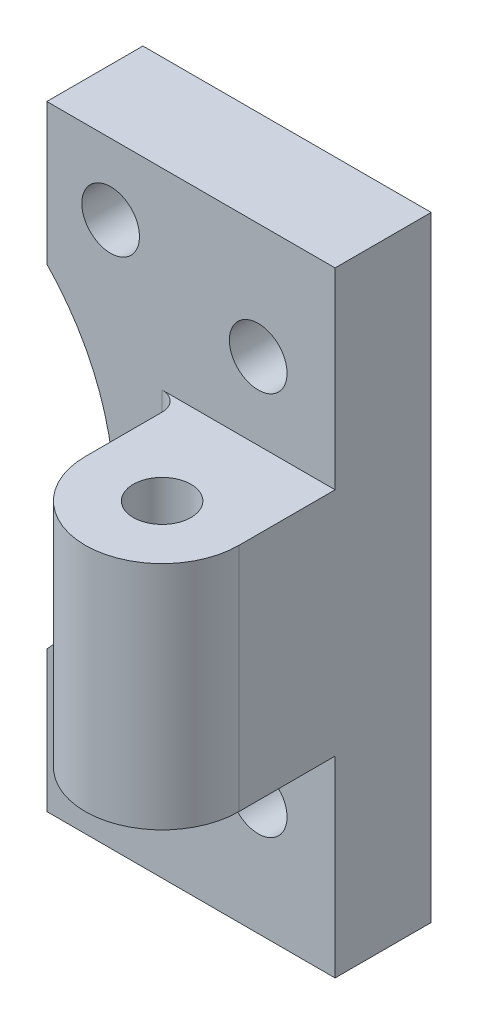
SolidWorks part; units mm, degrees
ref_plane "Front Plane" through (0, 0, 0) normal (0, 0, 1) x (1, 0, 0)
ref_plane "Top Plane" through (0, 0, 0) normal (0, 1, 0) x (1, 0, 0)
ref_plane "Right Plane" through (0, 0, 0) normal (1, 0, 0) x (0, 0, -1)
sketch "Sketch1" plane through (0, 0, 0) normal (0, 0, 1) x (1, 0, 0)
  line L1 (19.05, 12.7) -> (0, 12.7)
  line L2 (19.05, 12.7) -> (19.05, -12.7)
  line L3 (19.05, -12.7) -> (0, -12.7)
  line L4 (0, 12.7) -> (0, -12.7)
  line L5 (19.05, 12.7) -> (0, -12.7) construction
  line L6 (19.05, -12.7) -> (0, 12.7) construction
  point P0 (9.525, 0)
  dimension "D1" = 19.05
  dimension "D2" = 25.4
extrude "Boss-Extrude1" add sketch "Sketch1" along normal blind 3.9688
sketch "Sketch2" plane through (0, 0, 3.9688) normal (0, 0, 1) x (1, 0, 0)
  circle A0 centre (0, 0) radius 9.9219
  dimension "D1" = 19.8438
extrude "Cut-Extrude1" cut sketch "Sketch2" against normal through all
sketch "Sketch3" plane through (0, 0, 3.9688) normal (0, 0, 1) x (1, 0, 0)
  line L0 (0, 16.4323) -> (0, -17.8893) construction
  line L1 (-7.1985, 0) -> (7.9762, 0) construction
  line L2 (0, -12.7) -> (19.05, -12.7) construction
  line L3 (0, 12.7) -> (7.1437, 12.7)
  line L4 (0, 12.7) -> (0, -12.7)
  line L5 (0, -12.7) -> (7.1438, -12.7)
  line L6 (7.1437, 12.7) -> (7.1438, -12.7)
  line L7 (0, 12.7) -> (7.1438, -12.7) construction
  line L8 (0, -12.7) -> (7.1437, 12.7) construction
  point P13 (3.5719, 0)
  dimension "D4" = 14.2875
extrude "Cut-Extrude2" cut sketch "Sketch3" against normal through all
sketch "Sketch4" plane through (0, 0, 3.9688) normal (0, 0, 1) x (1, 0, 0)
  line L0 (19.05, -12.7) -> (19.05, 12.7) construction
  line L1 (19.05, 4.7625) -> (12.7, 4.7625)
  line L2 (19.05, 4.7625) -> (19.05, -4.7625)
  line L3 (19.05, -4.7625) -> (12.7, -4.7625)
  line L4 (12.7, 4.7625) -> (12.7, -4.7625)
  line L5 (19.05, 4.7625) -> (12.7, -4.7625) construction
  line L6 (19.05, -4.7625) -> (12.7, 4.7625) construction
  point P4 (15.875, 0)
  dimension "D1" = 9.525
  dimension "D2" = 6.35
extrude "Boss-Extrude2" add sketch "Sketch4" along normal blind 7.1437
hole_wizard "Tap Drill for #2 Helicoil1" positions "Sketch5" profile "Sketch6" hole size "#2-56" standard "ANSI Inch" end condition through all
sketch "Sketch5" plane through (0, 0, 0) normal (0, 0, -1) x (-1, 0, 0)
  line L0 (-12.5677, 0) -> (7.9862, 0) construction
  line L1 (0, 11.4341) -> (0, -12.6118) construction
  point P0 (-9.779, 9.779)
  point P2 (-9.779, -9.779)
  point P11 (-15.875, 7.9375)
  point P13 (-15.875, -7.9375)
  dimension "D1" = 19.558
  dimension "D2" = 19.558
  dimension "D3" = 31.75
  dimension "D4" = 15.875
sketch "Sketch6" plane through (9.779, 9.779, 0) normal (1, 0, 0) x (0, 1, 0)
  line L0 (0, 0) -> (0, 11.1125)
  line L1 (0, 11.1125) -> (1.1913, 11.1125)
  line L2 (1.1913, 11.1125) -> (1.1913, 0)
  line L5 (1.1913, 0) -> (0, 0)
  line L11 (0, -6.35) -> (0, 107.95) construction
  dimension "Thru Hole Dia." = 2.3825
  dimension "Thru Hole Depth" = 11.1125
hole_wizard "Tap Drill for #2 Helicoil3" positions "Sketch7" profile "Sketch8" hole size "#2-56" standard "ANSI Inch"
sketch "Sketch7" plane through (0, 4.7625, 0) normal (0, 1, 0) x (1, 0, 0)
  line L1 (19.05, -3.9688) -> (7.1438, -3.9688) construction
  line L2 (19.05, -11.1125) -> (12.7, -11.1125) construction
  point P0 (15.875, -7.9375)
  point P13 (15.875, -11.1125)
  dimension "D1" = 3.9688
sketch "Sketch8" plane through (15.875, 4.7625, 7.9375) normal (1, 0, 0) x (0, 0, 1)
  line L0 (0, 0) -> (0, 5.4529)
  line L1 (0, 5.4529) -> (1.1913, 4.7371)
  line L2 (1.1913, 4.7371) -> (1.1913, 0)
  line L5 (1.1913, 0) -> (0, 0)
  line L10 (0, 5.4529) -> (-1.1913, 4.7371) construction
  line L11 (0, -6.35) -> (0, 107.95) construction
  dimension "Hole Dia." = 2.3825
  dimension "Hole Depth" = 4.7371
  dimension "Drill Angle" = 118
hole_wizard "Tap Drill for #2 Helicoil3" positions "Sketch13" profile "Sketch14" hole size "#2-56" standard "ANSI Inch"
sketch "Sketch13" plane through (0, -4.7625, 0) normal (0, -1, 0) x (-1, 0, 0)
  point P0 (-15.875, -7.9375)
sketch "Sketch14" plane through (15.875, -4.7625, 7.9375) normal (1, 0, 0) x (0, 0, -1)
  line L0 (0, 0) -> (0, 5.4529)
  line L1 (0, 5.4529) -> (1.1913, 4.7371)
  line L2 (1.1913, 4.7371) -> (1.1913, 0)
  line L5 (1.1913, 0) -> (0, 0)
  line L10 (0, 5.4529) -> (-1.1913, 4.7371) construction
  line L11 (0, -6.35) -> (0, 107.95) construction
  dimension "Hole Dia." = 2.3825
  dimension "Hole Depth" = 4.7371
  dimension "Drill Angle" = 118
fillet "Fillet1" radius 0.7937 1 edges at (12.7, 0, 3.9688)
fillet "Fillet2" 2 edges at (12.7, 0, 11.1125) (19.05, 0, 11.1125) type full round first side face at (12.7, 0, 7.9375) second side face at (19.05, 0, 4.7625) middle face at (15.875, 0, 11.1125)
sketch "Sketch9" [suppressed] plane through (0, 0, 3.9688) normal (0, 0, 1) x (1, 0, 0)
  circle A0 centre (9.779, 9.779) radius 1.6891
  circle A1 centre (15.875, 7.9375) radius 1.6891
  circle A2 centre (15.875, -7.9375) radius 1.6891
  circle A3 centre (9.779, -9.779) radius 1.6891
  dimension "D1" = 3.3782
extrude "Cut-Extrude3" [suppressed] cut sketch "Sketch9" against normal through all
sketch "Sketch10" [suppressed] plane through (0, 4.7625, 0) normal (0, 1, 0) x (1, 0, 0)
  circle A0 centre (15.875, -7.9375) radius 1.6891
  dimension "D1" = 3.3782
extrude "Cut-Extrude4" [suppressed] cut sketch "Sketch10" against normal through all
